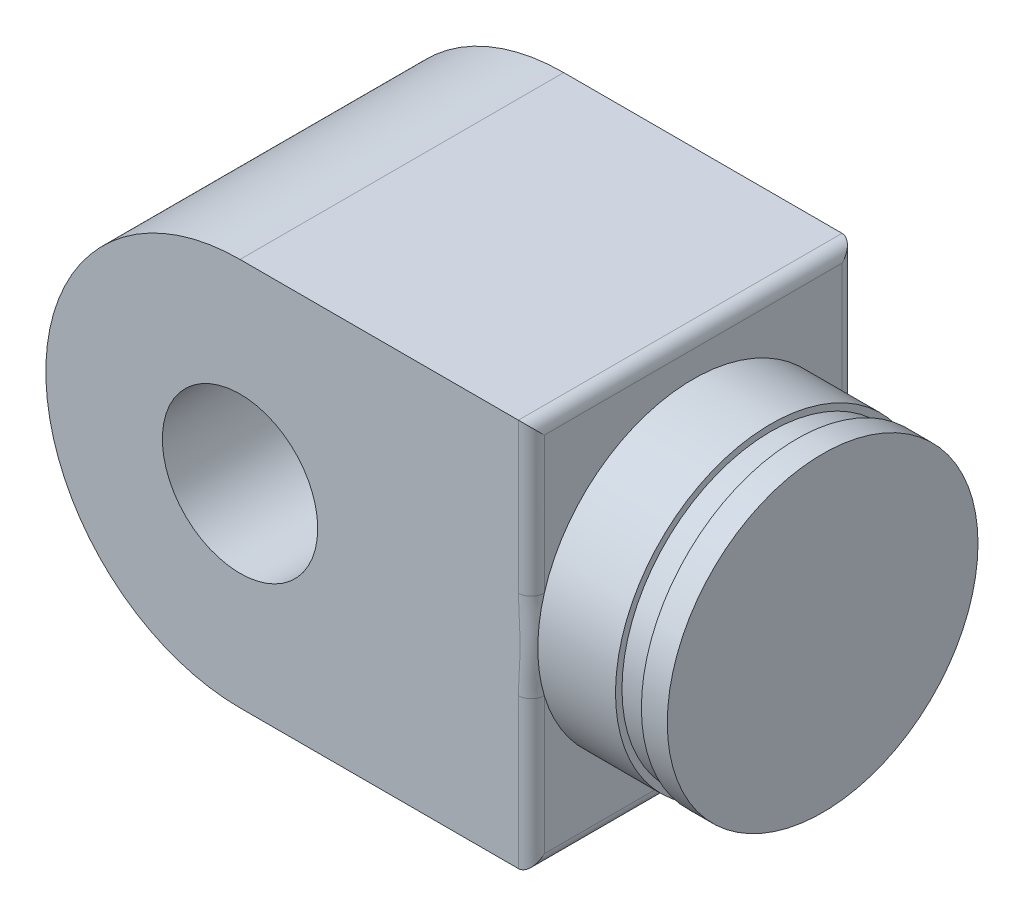
SolidWorks part; units mm, degrees
material "Alliage 6061"
ref_plane "Plan de face" through (0, 0, 0) normal (0, 0, 1) x (1, 0, 0)
ref_plane "Plan de dessus" through (0, 0, 0) normal (0, 1, 0) x (1, 0, 0)
ref_plane "Plan de droite" through (0, 0, 0) normal (1, 0, 0) x (0, 0, -1)
sketch "Esquisse1" plane through (0, 0, 0) normal (0, 0, 1) x (1, 0, 0)
  line L0 (0, 0) -> (45, 0) construction
  line L1 (0, -30) -> (45, -30)
  line L2 (45, -30) -> (45, 30)
  line L3 (45, 30) -> (0, 30)
  arc A0 (0, 30) -> (0, -30) centre (0, 0) ccw
  dimension "D1" = 30
  dimension "D2" = 45
extrude "Boss.-Extru.1" add sketch "Esquisse1" along normal mid plane 50
sketch "Esquisse2" plane through (0, 0, 25) normal (0, 0, 1) x (1, 0, 0)
  circle A0 centre (0, 0) radius 12
  dimension "D1" = 24
extrude "Enlèv. mat.-Extru.1" cut sketch "Esquisse2" against normal through all
sketch "Esquisse3" plane through (45, 0, 0) normal (1, 0, 0) x (0, 0, -1)
  circle A0 centre (0, 0) radius 24
  dimension "D1" = 48
extrude "Boss.-Extru.2" add sketch "Esquisse3" along normal blind 20
ref_plane "J5_Groove_Plane" through (61, 0, 0) normal (1, 0, 0) x (0, 0, -1)
sketch "Esquisse4" plane through (61, 0, 0) normal (1, 0, 0) x (0, 0, -1)
  circle A0 centre (0, 0) radius 24.5
  circle A1 centre (0, 0) radius 23
  dimension "D1" = 49
  dimension "D2" = 46
extrude "Enlèv. mat.-Extru.2" cut sketch "Esquisse4" against normal blind 4
fillet "Congé1" radius 2 4 edges at (45, 0, -25) (45, 0, 25) (45, 30, 0) (45, -30, 0) tangent propagation no
ref_axis "Axis_J4" through (0, 0, -25) along (0, 0, 1)
ref_axis "Axis_J5" through (65, 0, 0) along (-1, 0, 0)
